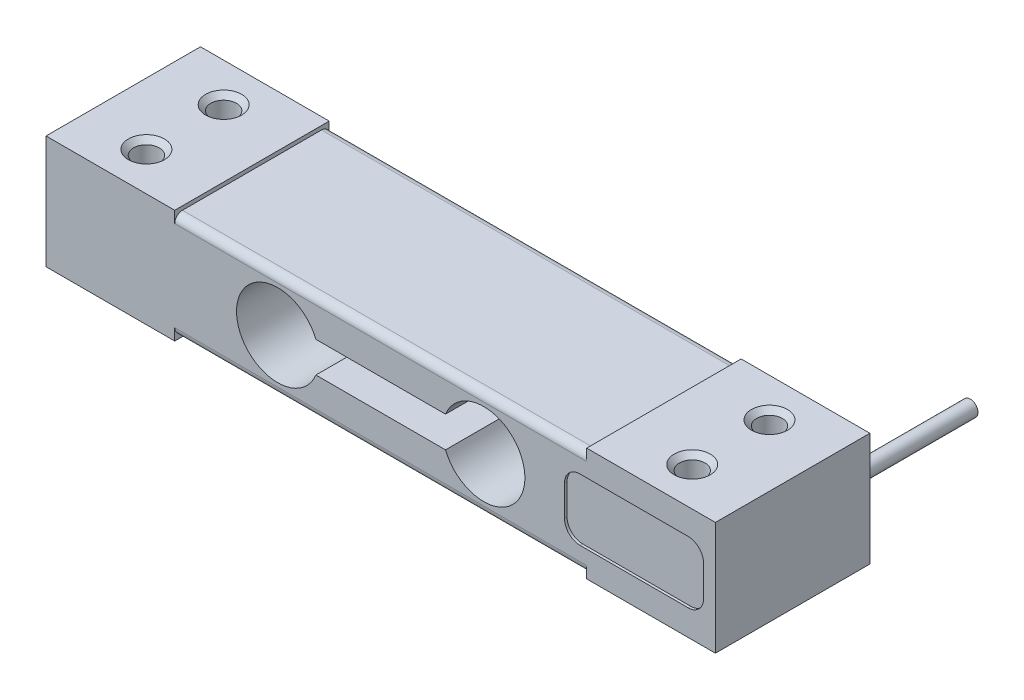
SolidWorks part; units mm, degrees
ref_plane "前视基准面" through (0, 0, 0) normal (0, 0, 1) x (1, 0, 0)
ref_plane "上视基准面" through (0, 0, 0) normal (0, 1, 0) x (1, 0, 0)
ref_plane "右视基准面" through (0, 0, 0) normal (1, 0, 0) x (0, 0, -1)
sketch "草图1" plane through (0, 0, 0) normal (0, 0, 1) x (1, 0, 0)
  line L0 (-40, 11) -> (-40, 8.75)
  line L1 (-65, 11) -> (-40, 11)
  line L2 (-65, 11) -> (-65, -11)
  line L3 (-65, -11) -> (-40, -11)
  line L4 (65, 11) -> (65, -11)
  line L5 (-40, 8.75) -> (40, 8.75)
  line L6 (40, -8.75) -> (40, -11)
  line L7 (-40, -8.75) -> (40, -8.75)
  line L8 (40, 11) -> (65, 11)
  line L11 (40, 11) -> (40, 8.75)
  line L12 (-40, -8.75) -> (-40, -11)
  line L13 (-12.5838, -3) -> (12.5838, -3)
  line L14 (40, -11) -> (65, -11)
  line L16 (-12.5838, 3) -> (12.5838, 3)
  arc A0 (-12.5838, 3) -> (-12.5838, -3) centre (-20, 0) ccw
  arc A1 (12.5838, -3) -> (12.5838, 3) centre (20, 0) ccw
  point P0 (0, 0)
  point P5 (0, 0)
  point P6 (0, 0)
  point P19 (-40, 0)
  point P22 (40, 0)
  dimension "D1" = 22
  dimension "D2" = 130
  dimension "D3" = 17.5
extrude "凸台-拉伸1" add sketch "草图1" along normal mid plane 30
sketch "草图2" plane through (0, 11, 0) normal (0, 1, 0) x (1, 0, 0)
  point P6 (-53, 7.5)
  point P8 (-53, -7.5)
  point P9 (53, 7.5)
  point P10 (53, -7.5)
hole_wizard "M6 螺纹孔1" positions "3D草图1" profile "草图3" tap size "M6" standard "GB" end condition through all
sketch3d "3D草图1"
  point P0 (-53, 11, -7.5)
  point P3 (-53, 11, 7.5)
  point P6 (53, 11, -7.5)
  point P9 (53, 11, 7.5)
sketch "草图3" plane through (-53, 11, -7.5) normal (1, 0, 0) x (0, 0, 1)
  line L0 (0, 0) -> (0, 22)
  line L1 (0, 22) -> (2.5, 22)
  line L2 (2.5, 22) -> (2.5, 0)
  line L5 (2.5, 0) -> (0, 0)
  line L11 (0, -6.35) -> (0, 107.95) construction
  dimension "通孔螺纹孔钻头直径" = 5
  dimension "通孔螺纹孔钻头深度" = 22
cosmetic thread "孔螺蚊线1" parameters "D2"=6
cosmetic thread "孔螺蚊线2" parameters "D2"=6
cosmetic thread "孔螺蚊线3" parameters "D2"=6
cosmetic thread "孔螺蚊线4" parameters "D2"=6
chamfer "倒角1" distance 1 angle 45 8 edges at (-53, -11, 10) (-53, -11, -5) (53, -11, -5) (53, -11, 10) (53, 11, 10) (53, 11, -5) (-53, 11, 10) (-53, 11, -5)
sketch "草图4" plane through (0, 0, 15) normal (0, 0, 1) x (1, 0, 0)
  line L1 (-40, 10.25) -> (40, 10.25)
  line L3 (-40, -10.25) -> (40, -10.25)
  line L12 (40, -11) -> (65, -11)
  line L13 (65, -11) -> (65, 11)
  line L14 (65, 11) -> (40, 11)
  line L15 (40, 11) -> (40, 8.75)
  line L16 (40, 8.75) -> (-40, 8.75)
  line L17 (-40, 8.75) -> (-40, 11)
  line L18 (-40, 11) -> (-65, 11)
  line L19 (-65, 11) -> (-65, -11)
  line L20 (-65, -11) -> (-40, -11)
  line L21 (-40, -11) -> (-40, -8.75)
  line L22 (-40, -8.75) -> (40, -8.75)
  line L23 (40, -8.75) -> (40, -11)
  line L27 (40, 10.25) -> (40, 8.75)
  line L28 (40, 8.75) -> (-40, 8.75)
  line L29 (-40, 8.75) -> (-40, 10.25)
  line L33 (-40, -10.25) -> (-40, -8.75)
  line L34 (-40, -8.75) -> (40, -8.75)
  line L35 (40, -8.75) -> (40, -10.25)
  point P2 (0, 0)
  dimension "D1" = 0
extrude "凸台-拉伸2" add sketch "草图4" against normal blind 30 separate body
fillet "圆角1" radius 1.5 2 edges at (0, 10.25, -15) (0, 10.25, 15)
fillet "圆角2" radius 1.5 2 edges at (0, -10.25, -15) (0, -10.25, 15)
sketch "草图5" plane through (0, 0, 15) normal (0, 0, 1) x (1, 0, 0)
  line L0 (65, -11) -> (65, 11) construction
  line L1 (38.7, 6) -> (59.7, 6)
  line L2 (35.7, 3) -> (35.7, -3)
  line L3 (38.7, -6) -> (59.7, -6)
  line L4 (62.7, 3) -> (62.7, -3)
  line L5 (35.7, 6) -> (62.7, -6) construction
  line L6 (35.7, -6) -> (62.7, 6) construction
  arc A0 (62.7, -3) -> (59.7, -6) centre (59.7, -3) cw
  arc A1 (62.7, 3) -> (59.7, 6) centre (59.7, 3) ccw
  arc A2 (35.7, -3) -> (38.7, -6) centre (38.7, -3) ccw
  arc A3 (35.7, 3) -> (38.7, 6) centre (38.7, 3) cw
  point P0 (49.2, 0)
  dimension "D3" = 3
  dimension "D1" = 12
  dimension "D2" = 27
  dimension "D4" = 2.3
extrude "切除-拉伸1" cut sketch "草图5" against normal blind 0.5
sketch "草图6" plane through (0, 0, -15) normal (0, 0, -1) x (-1, 0, 0)
  line L0 (-65, -11) -> (-65, 11) construction
  circle A0 centre (-59.5, 0) radius 1.5
  dimension "D1" = 3
  dimension "D2" = 5.5
extrude "凸台-拉伸3" add sketch "草图6" along normal blind 25
sketch "草图7" plane through (0, 0, 15) normal (0, 0, 1) x (1, 0, 0)
  line L0 (56.4281, 237.8763) -> (530.4281, 237.8763) construction
